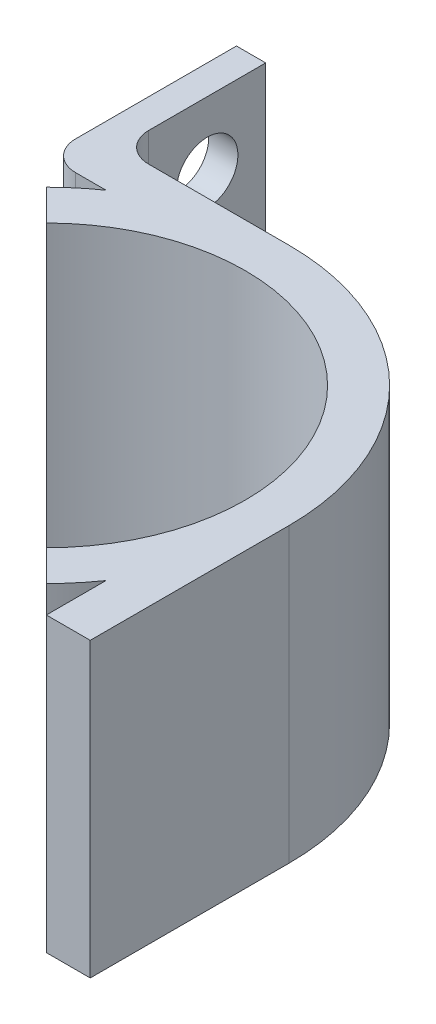
SolidWorks part; units mm, degrees
ref_plane "前视基准面" through (0, 0, 0) normal (0, 0, 1) x (1, 0, 0)
ref_plane "上视基准面" through (0, 0, 0) normal (0, 1, 0) x (1, 0, 0)
ref_plane "右视基准面" through (0, 0, 0) normal (1, 0, 0) x (0, 0, -1)
other "Configuration Table"
sketch "草图1" plane through (0, 0, 0) normal (0, 1, 0) x (1, 0, 0)
  line L3 (-16.6, -4.1781) -> (-30.2, -4.1781)
  line L4 (-30.2, -4.1781) -> (-30.2, -7.1781)
  line L5 (-30.2, -7.1781) -> (-26.1184, -7.1781)
  line L6 (-3, -30.2965) -> (-3, -34.3781)
  line L8 (0, -20.7781) -> (0, -34.3781)
  line L9 (0, -34.3781) -> (-3, -34.3781)
  line L12 (-26.2167, -11.1614) -> (-28.338, -9.0401)
  line L13 (-6.9833, -30.3947) -> (-4.862, -32.516)
  arc A0 (-16.6, -7.1781) -> (-3, -20.7781) centre (-16.6, -20.7781) cw
  arc A1 (0, -20.7781) -> (-16.6, -4.1781) centre (-16.6, -20.7781) ccw
  arc A2 (-5.4578, -28.5763) -> (-24.3982, -9.6359) centre (-16.6, -20.7781) ccw
  arc A3 (0, -20.7781) -> (-16.6, -4.1781) centre (-16.6, -20.7781) ccw
  arc A4 (-6.9833, -30.3947) -> (-26.2167, -11.1614) centre (-16.6, -20.7781) ccw
  arc A5 (-4.862, -32.516) -> (-3, -30.2965) centre (-16.6, -20.7781) ccw
  arc A6 (-26.1184, -7.1781) -> (-28.338, -9.0401) centre (-16.6, -20.7781) ccw
  arc A7 (0, -20.7781) -> (-16.6, -4.1781) centre (-16.6, -20.7781) ccw
  dimension "D1" = 13.6
  dimension "D2" = 3
  dimension "D5" = 13.6
  dimension "D3" = 3
  dimension "D4" = 13.6
extrude "凸台-拉伸2" add sketch "草图1" along normal blind 20 contours A2 L6 L9 L8 A1 L3 L4 L5 A0 region at (-5.164, 0, 9.3421)
sketch "草图2" plane through (0, 20, 0) normal (0, 1, 0) x (1, 0, 0)
  line L0 (-30.2, -4.1781) -> (-30.2, 5.8219)
  line L1 (-30.2, 5.8219) -> (-28.2, 5.8219)
  line L2 (-28.2, 5.8219) -> (-28.2, -4.1781)
  line L3 (-16.6, -4.1781) -> (-30.2, -4.1781) construction
  line L4 (-28.2, -4.1781) -> (-30.2, -4.1781)
  dimension "D1" = 2
  dimension "D2" = 10
extrude "凸台-拉伸3" add sketch "草图2" against normal blind 20
fillet "圆角1" radius 2 1 edges at (-28.2, 10, 4.1781)
sketch "草图3" plane through (-28.2, 0, 0) normal (1, 0, 0) x (0, 0, -1)
  line L0 (5.8219, 0) -> (5.8219, 20) construction
  line L1 (-2.1781, 20) -> (5.8219, 20) construction
  line L2 (-2.1781, 0) -> (5.8219, 0) construction
  circle A0 centre (1.8219, 15.5) radius 2.1
  circle A1 centre (1.8219, 4.5) radius 2.1
  dimension "D1" = 4.2
  dimension "D2" = 4.2
  dimension "D3" = 4
  dimension "D4" = 4
  dimension "D5" = 4.5
  dimension "D6" = 4.5
extrude "切除-拉伸1" cut sketch "草图3" against normal blind 20
fillet "圆角2" radius 2 1 edges at (-30.2, 10, 7.1781)
